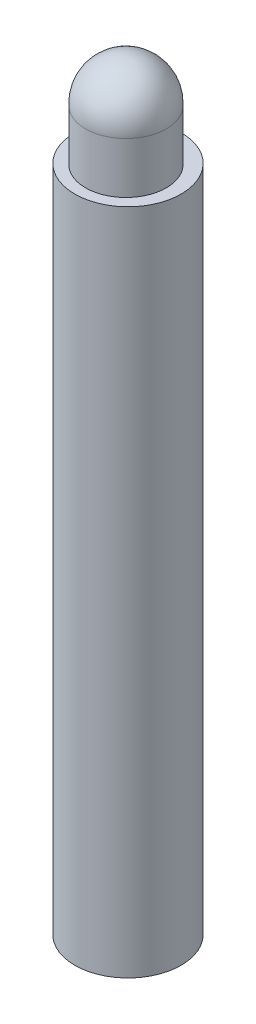
SolidWorks part; units mm, degrees
ref_plane "Front Plane" through (0, 0, 0) normal (0, 0, 1) x (1, 0, 0)
ref_plane "Top Plane" through (0, 0, 0) normal (0, 1, 0) x (1, 0, 0)
ref_plane "Right Plane" through (0, 0, 0) normal (1, 0, 0) x (0, 0, -1)
sketch "Sketch1" plane through (0, 0, 0) normal (0, 1, 0) x (1, 0, 0)
  circle A0 centre (0, 0) radius 1.25
  dimension "D1" = 2.5
extrude "Boss-Extrude1" add sketch "Sketch1" along normal blind 15.7
sketch "Sketch2" plane through (0, 0, 0) normal (0, -1, 0) x (1, 0, 0)
  circle A0 centre (0, 0) radius 0.85
  dimension "D1" = 1.7
extrude "Cut-Extrude1" cut sketch "Sketch2" against normal blind 0.5
sketch "Sketch4" plane through (0, 15.7, 0) normal (0, 1, 0) x (1, 0, 0)
  circle A0 centre (0, -0.0477) radius 0.95
  dimension "D1" = 1.9
extrude "Boss-Extrude2" add sketch "Sketch4" along normal blind 1.2
dome "Dome1" faces to dome 1 distance 1 reverse direction no elliptical dome no face at (0, 16.9, 0.9977) parameters "D1"=1
